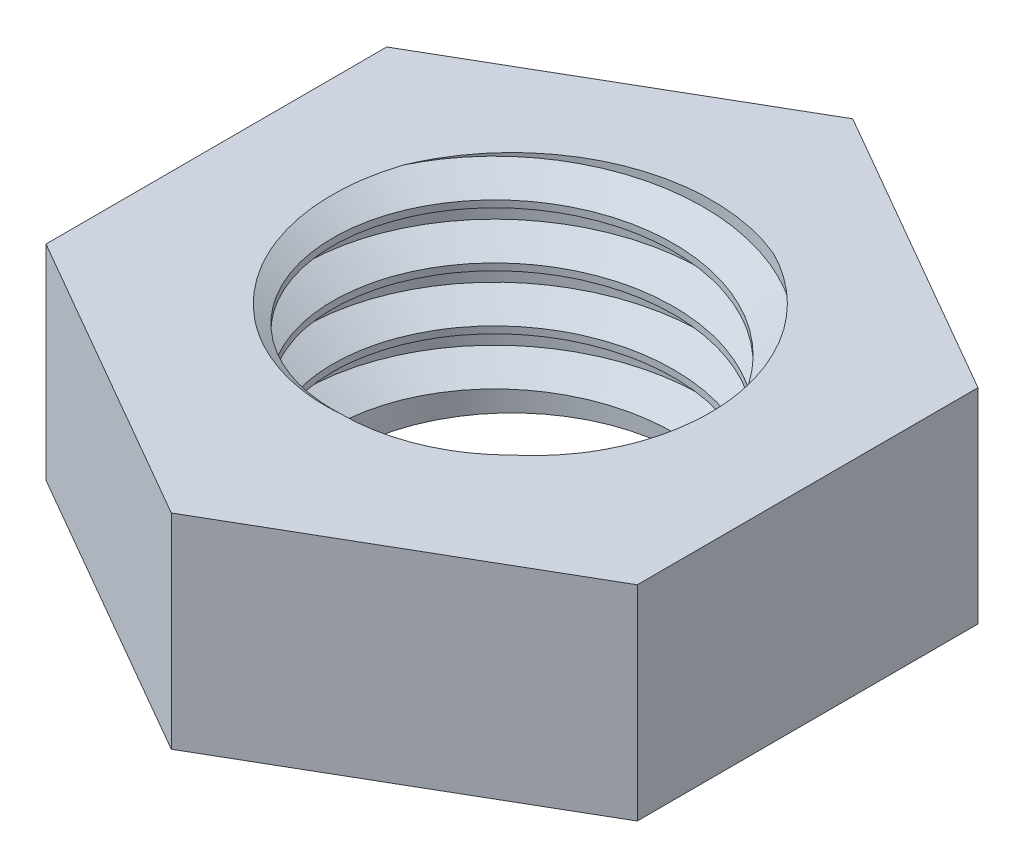
SolidWorks part; units mm, degrees
ref_plane "Front Plane" through (0, 0, 0) normal (0, 0, 1) x (1, 0, 0)
ref_plane "Top Plane" through (0, 0, 0) normal (0, 1, 0) x (1, 0, 0)
ref_plane "Right Plane" through (0, 0, 0) normal (1, 0, 0) x (0, 0, -1)
sketch "Sketch1" plane through (0, 0, 0) normal (0, 1, 0) x (1, 0, 0)
  line L1 (21.6625, -12.4795) -> (21.6388, 12.5205)
  line L2 (21.6388, 12.5205) -> (-0.0237, 25)
  line L3 (-0.0237, 25) -> (-21.6625, 12.4795)
  line L4 (-21.6625, 12.4795) -> (-21.6388, -12.5205)
  line L5 (-21.6388, -12.5205) -> (0.0237, -25)
  line L6 (0.0237, -25) -> (21.6625, -12.4795)
  circle A0 centre (0, 0) radius 21.6506 construction
  circle A1 centre (0, 0) radius 12.5
  dimension "D2" = 25
  dimension "D1" = 25
extrude "Boss-Extrude1" add sketch "Sketch1" along normal blind 15
thread "Thread1" pitch 4 method cut profile "Thread Profile2" start angle 0, offset 0, length 0, pitch 4, diameter 25
ref_plane "Plane2" through (12.5, 0, 0) normal (0, 0, -1) x (-1, 0, 0)
sketch "Thread Profile2" plane through (12.5, 0, 0) normal (0, 0, -1) x (-1, 0, 0)
  line L0 (0, 0) -> (0, 4) construction
  line L11 (0, 0) -> (0, 3.5)
  line L12 (0, 3.5) -> (-2.1651, 2.25)
  line L13 (-2.1651, 2.25) -> (-2.1651, 1.25)
  line L15 (-2.1651, 1.25) -> (0, 0)
  line L17 (-2.1651, 1.75) -> (0, 1.75) construction
  point P2 (0, 0)
  dimension "Pitch" = 4
  dimension "Profile_Angle" = 60
  dimension "Profile_Land" = 1
  dimension "Profile_Height" = 2.1651
